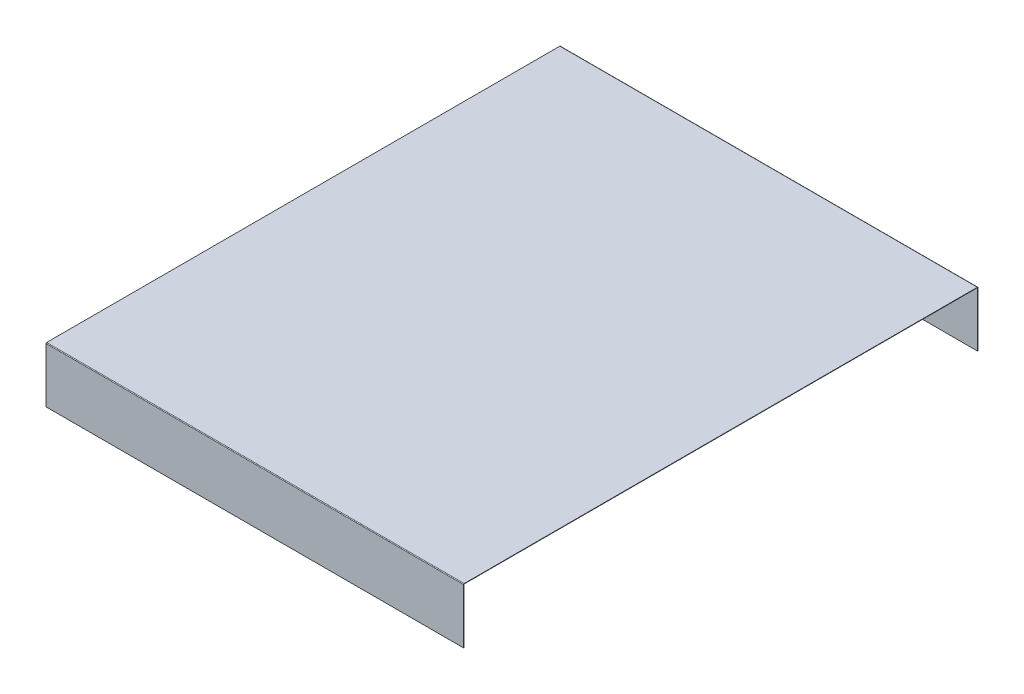
SolidWorks part; units mm, degrees
note: The reader was unsure of these and kept them because the rebuilt part matched: thickness of "Brida base1", "Brida de arista1", "Chapa metálica1", "Chapa metálica2"; flange length of "Brida de arista1".
ref_plane "Alzado" through (0, 0, 0) normal (0, 0, 1) x (1, 0, 0)
ref_plane "Planta" through (0, 0, 0) normal (0, 1, 0) x (1, 0, 0)
ref_plane "Vista lateral" through (0, 0, 0) normal (1, 0, 0) x (0, 0, -1)
sketch "Croquis1" plane through (0, 0, 0) normal (0, 1, 0) x (1, 0, 0)
  line L1 (0, 0) -> (1220, 0)
  line L2 (0, 0) -> (0, -1503)
  line L3 (0, -1503) -> (1220, -1503)
  line L4 (1220, 0) -> (1220, -1503)
  dimension "D1" = 1503
  dimension "D2" = 1220
base flange "Brida base1" sketch "Croquis1" thickness 1.214 reverse thickness direction no parameters "D1"=0.7366
edge flange "Brida de arista1" sketch "Croquis10" flange profiles "Croquis10", "Croquis11" flange angle 90 flange length 162 flange position material inside bend radius 0.7366 thickness 1.214 relief rectangular parameters "D6"=10, "D8"=0.5
sketch "Croquis10" plane through (0, -1.214, 0) normal (0, 0, -1) x (1, 0, 0)
  line L2 (0, 0) -> (0, 160.786)
  line L3 (0, 160.786) -> (1220, 160.786)
  line L4 (1220, 160.786) -> (1220, 0)
  line L5 (1220, 0) -> (0, 0) construction
  line L6 (1220, 0) -> (0, 0)
sketch "Croquis11" plane through (0, -1.214, 1503) normal (0, 0, 1) x (-1, 0, 0)
  line L0 (0, 0) -> (-1220, 0) construction
  line L1 (0, 0) -> (-1220, 0)
  line L2 (-1220, 0) -> (-1220, 160.786)
  line L3 (-1220, 160.786) -> (0, 160.786)
  line L4 (0, 160.786) -> (0, 0)
bend "Pliegue de arista1" bend radius 0.7366 bend angle 90 parameters "D5"=1
bend "Pliegue de arista2" bend radius 0.7366 bend angle 90 parameters "D5"=2
sketch "Líneas de pliegue1" [suppressed] plane through (0, 0, 0) normal (0, 1, 0) x (1, 0, 0)
sketch "Cuadro delimitador1" [suppressed] plane through (0, 0, 0) normal (0, 1, 0) x (1, 0, 0)
sheet metal parameters "Chapa metálica1" thickness 1.214 parameters "D1"=0.7366
flat pattern "Chapa desplegada1" [suppressed]
sketch "Líneas de pliegue2" plane through (0, 0, 0) normal (0, 1, 0) x (1, 0, 0)
sketch3d "Cuadro delimitador2" [suppressed]
  line L0 (0, 0, 0) -> (0, -1500, 0) construction
  line L1 (-1220, 0, 0) -> (-1220, -1500, 0) construction
  line L2 (0, 0, 0) -> (-1220, 0, 0) construction
  line L3 (0, -1500, 0) -> (-1220, -1500, 0) construction
sheet metal parameters "Chapa metálica2" thickness 1.214 parameters "D1"=0.7366, "D7"=1.9
flat pattern "Chapa desplegada1"
sketch "Líneas de pliegue2" plane through (0, 0, 0) normal (0, 1, 0) x (1, 0, 0)
  line L0 (0, -1502.1047) -> (1220, -1502.1047) construction
  line L1 (1220, -0.8953) -> (0, -0.8953) construction
  line L2 (0, -1502.1047) -> (1220, -1502.1047) construction
  line L3 (1220, -0.8953) -> (0, -0.8953) construction
sketch3d "Cuadro delimitador2" [suppressed]
  line L0 (0, 160.2093, 0) -> (0, -1663.2093, 0) construction
  line L1 (1220, 160.2093, 0) -> (1220, -1663.2093, 0) construction
  line L2 (0, 160.2093, 0) -> (1220, 160.2093, 0) construction
  line L3 (0, -1663.2093, 0) -> (1220, -1663.2093, 0) construction
bend of the flat pattern "Aplanar-<Pliegue de arista1>1"
bend of the flat pattern "Aplanar-<Pliegue de arista2>1"
